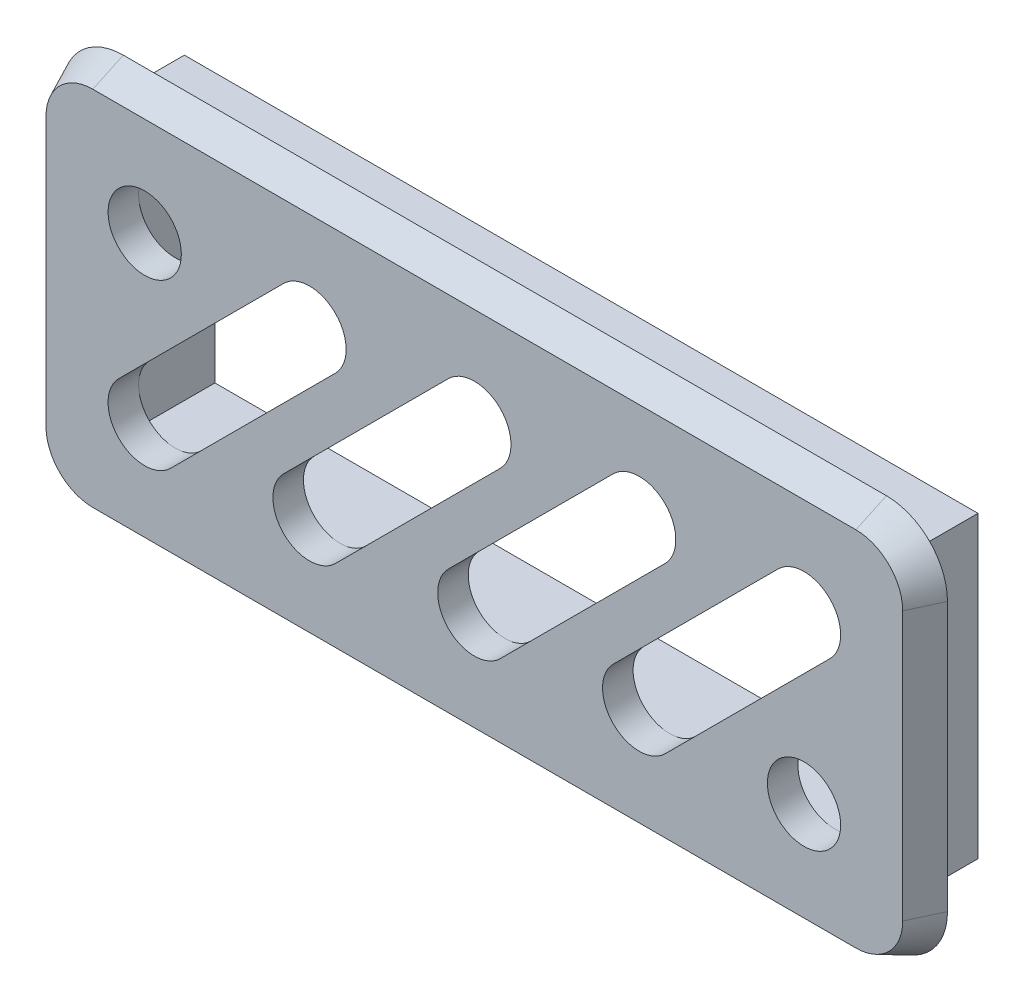
SolidWorks part; units mm, degrees
ref_plane "前视基准面" through (0, 0, 0) normal (0, 0, 1) x (1, 0, 0)
ref_plane "上视基准面" through (0, 0, 0) normal (0, 1, 0) x (1, 0, 0)
ref_plane "右视基准面" through (0, 0, 0) normal (1, 0, 0) x (0, 0, -1)
other "Configuration Table"
sketch "草图1" plane through (0, 0, 0) normal (0, 0, 1) x (1, 0, 0)
  line L4 (32.6638, -12.1008) -> (32.6638, -4.3008)
  line L5 (32.6638, -4.3008) -> (8.6638, -4.3008)
  line L6 (8.6638, -4.3008) -> (8.6638, -12.1008)
  line L7 (8.6638, -12.1008) -> (32.6638, -12.1008)
  line L8 (33.6638, -13.1008) -> (33.6638, -3.3008)
  line L9 (7.6638, -13.1008) -> (33.6638, -13.1008)
  line L10 (7.6638, -3.3008) -> (7.6638, -13.1008)
  line L11 (33.6638, -3.3008) -> (7.6638, -3.3008)
  line L12 (33.6638, -13.1008) -> (33.6638, -3.3008)
  line L13 (7.6638, -13.1008) -> (33.6638, -13.1008)
  line L14 (7.6638, -3.3008) -> (7.6638, -13.1008)
  line L15 (33.6638, -3.3008) -> (7.6638, -3.3008)
  dimension "D1" = 0.1
extrude "凸台-拉伸1" add sketch "草图1" against normal blind 2.5
sketch "草图2" plane through (0, 0, 0) normal (0, 0, 1) x (1, 0, 0)
  line L8 (35.1638, -14.6008) -> (35.1638, -1.8008)
  line L9 (6.1638, -14.6008) -> (35.1638, -14.6008)
  line L10 (6.1638, -1.8008) -> (6.1638, -14.6008)
  line L11 (35.1638, -1.8008) -> (6.1638, -1.8008)
  line L12 (35.1638, -12.6008) -> (35.1638, -3.8008)
  line L13 (8.1638, -14.6008) -> (33.1638, -14.6008)
  line L14 (6.1638, -3.8008) -> (6.1638, -12.6008)
  line L15 (33.1638, -1.8008) -> (8.1638, -1.8008)
  arc A0 (35.1638, -3.8008) -> (33.1638, -1.8008) centre (33.1638, -3.8008) ccw
  arc A1 (35.1638, -12.6008) -> (33.1638, -14.6008) centre (33.1638, -12.6008) cw
  arc A2 (8.1638, -14.6008) -> (6.1638, -12.6008) centre (8.1638, -12.6008) cw
  arc A3 (6.1638, -3.8008) -> (8.1638, -1.8008) centre (8.1638, -3.8008) cw
  dimension "D2" = 2
  dimension "D1" = 1.5
extrude "凸台-拉伸2" add sketch "草图2" along normal blind 1 draft 25
sketch "草图3" plane through (0, 0, 0) normal (0, 0, -1) x (-1, 0, 0)
  line L0 (-31.4638, -5.5008) -> (-26.0638, -10.9008) construction
  line L1 (-30.6153, -4.6523) -> (-25.2153, -10.0523)
  line L2 (-45.8827, -5.5008) -> (-41.0684, -5.5008) construction
  line L6 (-32.3124, -6.3493) -> (-26.9124, -11.7493)
  line L7 (-26.0638, -5.5008) -> (-20.6638, -10.9008) construction
  line L10 (-50.9645, -10.9008) -> (-43.5902, -10.9008) construction
  line L13 (-25.2153, -4.6523) -> (-19.8153, -10.0523)
  line L16 (-26.9124, -6.3493) -> (-21.5124, -11.7493)
  line L19 (-32.6638, -12.1008) -> (-32.6638, -4.3008) construction
  line L22 (-20.6638, -5.5008) -> (-15.2638, -10.9008) construction
  line L25 (-8.6638, -12.1008) -> (-32.6638, -12.1008) construction
  line L26 (-19.8153, -4.6523) -> (-14.4153, -10.0523)
  line L27 (-21.5124, -6.3493) -> (-16.1124, -11.7493)
  line L28 (-15.2638, -5.5008) -> (-9.8638, -10.9008) construction
  line L29 (-14.4153, -4.6523) -> (-9.0153, -10.0523)
  line L30 (-16.1124, -6.3493) -> (-10.7124, -11.7493)
  line L32 (-32.6638, -4.3008) -> (-8.6638, -4.3008) construction
  circle A74 centre (-31.4638, -10.9008) radius 1.2
  arc A75 (-30.6153, -4.6523) -> (-32.3124, -6.3493) centre (-31.4638, -5.5008) ccw
  arc A76 (-26.9124, -11.7493) -> (-25.2153, -10.0523) centre (-26.0638, -10.9008) ccw
  arc A77 (-25.2153, -4.6523) -> (-26.9124, -6.3493) centre (-26.0638, -5.5008) ccw
  arc A78 (-21.5124, -11.7493) -> (-19.8153, -10.0523) centre (-20.6638, -10.9008) ccw
  arc A79 (-19.8153, -4.6523) -> (-21.5124, -6.3493) centre (-20.6638, -5.5008) ccw
  arc A80 (-16.1124, -11.7493) -> (-14.4153, -10.0523) centre (-15.2638, -10.9008) ccw
  arc A81 (-14.4153, -4.6523) -> (-16.1124, -6.3493) centre (-15.2638, -5.5008) ccw
  arc A82 (-10.7124, -11.7493) -> (-9.0153, -10.0523) centre (-9.8638, -10.9008) ccw
  circle A83 centre (-9.8638, -5.5008) radius 1.2
  point P15 (-28.7638, -8.2008)
  point P23 (-23.3638, -8.2008)
  point P30 (-17.9638, -8.2008)
  point P37 (-12.5638, -8.2008)
  point P43 (0, 0)
  dimension "D3" = 5.4
  dimension "D2" = 1.2
  dimension "D1" = 1.2
  dimension "D4" = 4
extrude "切除-拉伸1" cut sketch "草图3" against normal up to next
